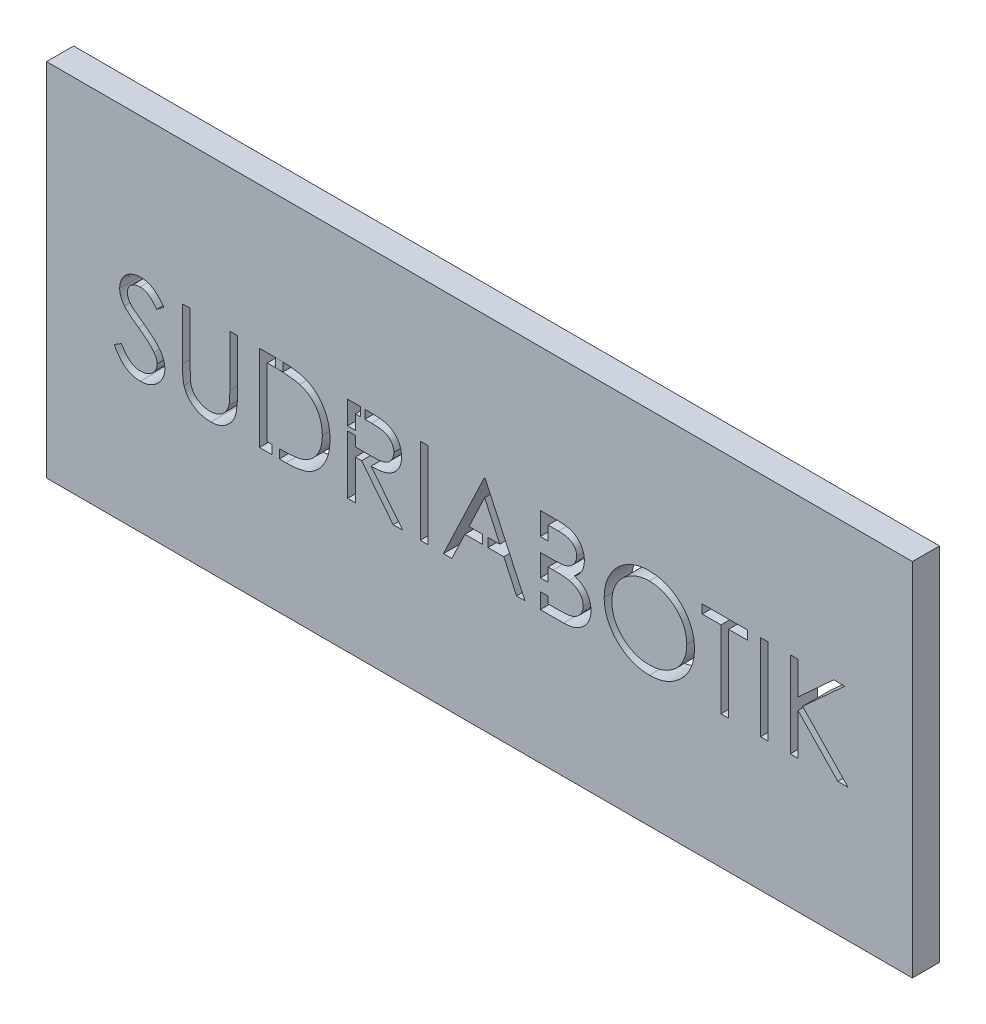
SolidWorks part; units mm, degrees
ref_plane "Plan de face" through (0, 0, 0) normal (0, 0, 1) x (1, 0, 0)
ref_plane "Plan de dessus" through (0, 0, 0) normal (0, 1, 0) x (1, 0, 0)
ref_plane "Plan de droite" through (0, 0, 0) normal (1, 0, 0) x (0, 0, -1)
sketch "Esquisse1" plane through (0, 0, 0) normal (0, 0, 1) x (1, 0, 0)
  line L0 (97.3951, 0) -> (-118.5049, 0) construction
  line L1 (-165, 119) -> (165, 119)
  line L2 (-165, 119) -> (-165, -119)
  line L3 (-165, -119) -> (165, -119)
  line L4 (165, 119) -> (165, -119)
  line L5 (0, 79.3588) -> (0, -79.3588) construction
  line L6 (-92.5, -55) -> (-77.5, -55)
  line L7 (-92.5, -55) -> (-92.5, -61)
  line L8 (-92.5, -61) -> (-77.5, -61)
  line L9 (-77.5, -55) -> (-77.5, -61)
  line L10 (-7.5, -55) -> (7.5, -55)
  line L11 (-7.5, -55) -> (-7.5, -61)
  line L12 (-7.5, -61) -> (7.5, -61)
  line L13 (7.5, -55) -> (7.5, -61)
  line L14 (77.5, -55) -> (92.5, -55)
  line L15 (77.5, -55) -> (77.5, -61)
  line L16 (77.5, -61) -> (92.5, -61)
  line L17 (92.5, -55) -> (92.5, -61)
  line L18 (-225.3679, 76) -> (203.1013, 76) construction
  line L19 (55, 99) -> (75, 99)
  line L20 (55, 99) -> (55, 93)
  line L21 (55, 93) -> (75, 93)
  line L22 (75, 99) -> (75, 93)
  line L23 (85, 99) -> (105, 99)
  line L24 (85, 99) -> (85, 93)
  line L25 (85, 93) -> (105, 93)
  line L26 (105, 99) -> (105, 93)
  circle A0 centre (-125, 76) radius 8
  circle A1 centre (125, 76) radius 8
  dimension "D23" = 16
  dimension "D24" = 16
  dimension "D1" = 238
  dimension "D2" = 330
  dimension "D3" = 165
  dimension "D4" = 119
  dimension "D5" = 15
  dimension "D6" = 6
  dimension "D7" = 6
  dimension "D8" = 15
  dimension "D9" = 6
  dimension "D10" = 15
  dimension "D11" = 70
  dimension "D12" = 70
  dimension "D13" = 58
  dimension "D14" = 72.5
  dimension "D15" = 6
  dimension "D16" = 20
  dimension "D17" = 20
  dimension "D18" = 6
  dimension "D19" = 10
  dimension "D20" = 60
  dimension "D21" = 20
  dimension "D22" = 20
  dimension "D25" = 40
  dimension "D26" = 40
  dimension "D27" = 195
extrude "Boss.-Extru.1" add sketch "Esquisse1" along normal blind 6
sketch "Esquisse2" plane through (0, 0, 6) normal (0, 0, 1) x (1, 0, 0)
  line L0 (243.146, 0) -> (-260.0003, 0) construction
  line L1 (0, 180.4713) -> (0, -129.6072) construction
  line L2 (165, 119) -> (-165, 119) construction
  line L3 (-115, 119) -> (-95, 119)
  line L4 (-115, 119) -> (-115, 125)
  line L5 (-115, 125) -> (-95, 125)
  line L6 (-95, 119) -> (-95, 125)
  line L7 (-165, 119) -> (-165, -119) construction
  line L8 (-45, 119) -> (-25, 119)
  line L9 (-45, 119) -> (-45, 125)
  line L10 (-45, 125) -> (-25, 125)
  line L11 (-25, 119) -> (-25, 125)
  line L12 (25, 119) -> (25, 125)
  line L13 (45, 125) -> (25, 125)
  line L14 (45, 119) -> (45, 125)
  line L15 (45, 119) -> (25, 119)
  line L16 (95, 119) -> (95, 125)
  line L17 (115, 125) -> (95, 125)
  line L18 (115, 119) -> (115, 125)
  line L19 (115, 119) -> (95, 119)
  line L20 (-115, 119) -> (-95, 119)
  line L21 (-115, 119) -> (-115, 125)
  line L22 (-115, 125) -> (-95, 125)
  line L23 (-95, 119) -> (-95, 125)
  line L24 (-45, 119) -> (-25, 119)
  line L25 (-45, 119) -> (-45, 125)
  line L26 (-45, 125) -> (-25, 125)
  line L27 (-25, 119) -> (-25, 125)
  line L28 (25, 119) -> (25, 125)
  line L29 (45, 125) -> (25, 125)
  line L30 (45, 119) -> (45, 125)
  line L31 (45, 119) -> (25, 119)
  line L32 (95, 119) -> (95, 125)
  line L33 (115, 125) -> (95, 125)
  line L34 (115, 119) -> (115, 125)
  line L35 (115, 119) -> (95, 119)
  line L36 (115, -119) -> (95, -119)
  line L37 (115, -119) -> (115, -125)
  line L38 (115, -125) -> (95, -125)
  line L39 (95, -119) -> (95, -125)
  line L40 (45, -119) -> (25, -119)
  line L41 (45, -119) -> (45, -125)
  line L42 (45, -125) -> (25, -125)
  line L43 (25, -119) -> (25, -125)
  line L44 (-25, -119) -> (-25, -125)
  line L45 (-45, -125) -> (-25, -125)
  line L46 (-45, -119) -> (-45, -125)
  line L47 (-45, -119) -> (-25, -119)
  line L48 (-95, -119) -> (-95, -125)
  line L49 (-115, -125) -> (-95, -125)
  line L50 (-115, -119) -> (-115, -125)
  line L51 (-115, -119) -> (-95, -119)
  line L52 (115, -119) -> (95, -119)
  line L53 (115, -119) -> (115, -125)
  line L54 (115, -125) -> (95, -125)
  line L55 (95, -119) -> (95, -125)
  line L56 (45, -119) -> (25, -119)
  line L57 (45, -119) -> (45, -125)
  line L58 (45, -125) -> (25, -125)
  line L59 (25, -119) -> (25, -125)
  line L60 (-25, -119) -> (-25, -125)
  line L61 (-45, -125) -> (-25, -125)
  line L62 (-45, -119) -> (-45, -125)
  line L63 (-45, -119) -> (-25, -119)
  line L64 (-95, -119) -> (-95, -125)
  line L65 (-115, -125) -> (-95, -125)
  line L66 (-115, -119) -> (-115, -125)
  line L67 (-115, -119) -> (-95, -119)
  line M9 (-165, -119) -> (165, -119)
  line M11 (165, 119) -> (-165, 119)
  dimension "D1" = 6
  dimension "D2" = 6
  dimension "D3" = 20
  dimension "D4" = 20
  dimension "D5" = 50
  dimension "D6" = 50
extrude "Boss.-Extru.2" add sketch "Esquisse2" against normal blind 6 contours L6 L5 L4 M11 | L11 L10 L9 M11 | L14 L13 L12 M11 | L18 L17 L16 M11 | L39 L38 L37 M9 | L43 L42 L41 M9 | L46 L45 L44 M9 | L50 L49 L48 M9 region at (-105, 122, 6) region at (105, 122, 6) region at (35, 122, 6) region at (-35, 122, 6) region at (105, -122, 6) region at (-105, -122, 6) region at (-35, -122, 6) region at (35, -122, 6)
sketch "Esquisse3" plane through (0, 0, 6) normal (0, 0, 1) x (1, 0, 0)
  line L0 (-165, 119) -> (-165, -119) construction
  line L1 (-165, 69) -> (-159, 69)
  line L2 (-165, 69) -> (-165, 89)
  line L3 (-165, 89) -> (-159, 89)
  line L4 (-159, 69) -> (-159, 89)
  line L5 (234.1368, 0) -> (-337.9213, 0) construction
  line L6 (-165, 29) -> (-159, 29)
  line L7 (-165, 29) -> (-165, 9)
  line L8 (-165, 9) -> (-159, 9)
  line L9 (-159, 29) -> (-159, 9)
  line L10 (0, 279.7488) -> (0, -188.1201) construction
  line L11 (-115, 119) -> (-165, 119) construction
  line L12 (-159, -29) -> (-159, -9)
  line L13 (-165, -9) -> (-159, -9)
  line L14 (-165, -29) -> (-165, -9)
  line L15 (-165, -29) -> (-159, -29)
  line L16 (-159, -69) -> (-159, -89)
  line L17 (-165, -89) -> (-159, -89)
  line L18 (-165, -69) -> (-165, -89)
  line L19 (-165, -69) -> (-159, -69)
  line L20 (165, -69) -> (159, -69)
  line L21 (165, -69) -> (165, -89)
  line L22 (165, -89) -> (159, -89)
  line L23 (159, -69) -> (159, -89)
  line L24 (165, -29) -> (159, -29)
  line L25 (165, -29) -> (165, -9)
  line L26 (165, -9) -> (159, -9)
  line L27 (159, -29) -> (159, -9)
  line L28 (159, 29) -> (159, 9)
  line L29 (165, 9) -> (159, 9)
  line L30 (165, 29) -> (165, 9)
  line L31 (165, 29) -> (159, 29)
  line L32 (159, 69) -> (159, 89)
  line L33 (165, 89) -> (159, 89)
  line L34 (165, 69) -> (165, 89)
  line L35 (165, 69) -> (159, 69)
  line L36 (153, -119) -> (153, -109)
  line L37 (-165, -119) -> (-153, -119)
  line L38 (-165, -119) -> (-165, -109)
  line L39 (-165, -109) -> (-153, -109)
  line L40 (-153, -119) -> (-153, -109)
  line L41 (165, -109) -> (153, -109)
  line L42 (165, -119) -> (165, -109)
  line L43 (165, -119) -> (153, -119)
  dimension "D1" = 40
  dimension "D2" = 6
  dimension "D3" = 6
  dimension "D4" = 20
  dimension "D5" = 20
  dimension "D6" = 30
  dimension "D7" = 12
  dimension "D8" = 10
extrude "Enlèv. mat.-Extru.1" cut sketch "Esquisse3" against normal blind 6
sketch "Esquisse4" plane through (0, 0, 6) normal (0, 0, 1) x (1, 0, 0)
  line L0 (-162, 122) -> (-162, -131.0602) construction
  line L1 (0, 158.5579) -> (0, -182.4489) construction
  line L2 (-115, 119) -> (-165, 119) construction
  line L3 (-106.4439, -58) -> (117.3944, -58) construction
  line L4 (-159, 89) -> (-165, 89) construction
  line L5 (-165, 119) -> (-165, 89) construction
  line L6 (-165, 69) -> (-159, 69) construction
  line L7 (-159, 29) -> (-165, 29) construction
  line L8 (-165, 9) -> (-159, 9) construction
  line L9 (-159, -9) -> (-165, -9) construction
  line L10 (-92.5, -55) -> (-92.5, -61) construction
  line L11 (-77.5, -61) -> (-77.5, -55) construction
  line L12 (-165, -29) -> (-159, -29) construction
  line L13 (-159, -69) -> (-165, -69) construction
  line L14 (-165, -89) -> (-159, -89) construction
  line L15 (-7.5, -55) -> (-7.5, -61) construction
  line L16 (162, 122) -> (162, -131.0602) construction
  line L17 (116.5184, 96) -> (43.4816, 96) construction
  line L18 (-126.5544, 122) -> (2.7821, 122) construction
  line L19 (-45, 119) -> (-95, 119) construction
  line L20 (-45, 119) -> (-45, 125) construction
  line L21 (75, 93) -> (75, 99) construction
  line L23 (55, 93) -> (75, 93) construction
  circle A0 centre (-162, 114) radius 1.5
  circle A1 centre (-162, 94) radius 1.5
  circle A2 centre (-162, 64) radius 1.5
  circle A3 centre (-162, 34) radius 1.5
  circle A4 centre (-162, 4) radius 1.5
  circle A5 centre (-105, 122) radius 1.5
  circle A6 centre (-162, -4) radius 1.5
  circle A7 centre (-162, -34) radius 1.5
  circle A8 centre (-162, -64) radius 1.5
  circle A9 centre (-162, -94) radius 1.5
  circle A10 centre (-97.5, -58) radius 1.5
  circle A11 centre (-72.5, -58) radius 1.5
  circle A12 centre (162, -94) radius 1.5
  circle A13 centre (162, -64) radius 1.5
  circle A14 centre (162, -34) radius 1.5
  circle A15 centre (162, -4) radius 1.5
  circle A16 centre (80, 96) radius 1.5
  circle A17 centre (162, 4) radius 1.5
  circle A18 centre (162, 34) radius 1.5
  circle A19 centre (162, 64) radius 1.5
  circle A20 centre (162, 94) radius 1.5
  circle A21 centre (162, 114) radius 1.5
  circle A22 centre (-12.5, -58) radius 1.5
  circle A23 centre (12.5, -58) radius 1.5
  circle A24 centre (72.5, -58) radius 1.5
  circle A25 centre (97.5, -58) radius 1.5
  circle A26 centre (-35, 122) radius 1.5
  circle A27 centre (35, 122) radius 1.5
  circle A28 centre (105, 122) radius 1.5
  dimension "D1" = 3
  dimension "D2" = 3
  dimension "D3" = 3
  dimension "D4" = 3
  dimension "D5" = 3
  dimension "D6" = 3
  dimension "D7" = 3
  dimension "D8" = 3
  dimension "D9" = 3
  dimension "D10" = 3
  dimension "D11" = 3
  dimension "D12" = 5
  dimension "D13" = 5
  dimension "D15" = 5
  dimension "D16" = 5
  dimension "D17" = 5
  dimension "D19" = 3
  dimension "D20" = 5
  dimension "D21" = 5
  dimension "D23" = 3
  dimension "D24" = 3
  dimension "D25" = 5
  dimension "D26" = 5
  dimension "D27" = 5
  dimension "D28" = 10
  dimension "D29" = 3
  dimension "D30" = 5
  dimension "D31" = 3
  dimension "D33" = 10
  dimension "D14" = 3
  dimension "D18" = 5
  dimension "D22" = 5
  dimension "D32" = 3
extrude "Enlèv. mat.-Extru.2" cut sketch "Esquisse4" against normal blind 6
sketch "Esquisse5" plane through (0, 0, 6) normal (0, 0, 1) x (1, 0, 0)
  line L1 (-200.0968, 0) -> (223.5072, 0)
  line L2 (-200.0968, 0) -> (-200.0968, -150.3561)
  line L3 (-200.0968, -150.3561) -> (223.5072, -150.3561)
  line L4 (223.5072, 0) -> (223.5072, -150.3561)
extrude "Enlèv. mat.-Extru.3" cut sketch "Esquisse5" against normal blind 6
sketch "Esquisse6" plane through (0, 0, 6) normal (0, 0, 1) x (1, 0, 0)
  line L0 (-165, 69) -> (-165, 29) construction
  line L2 (165, 0) -> (-165, 0) construction
  text T0 "SUDRIABOTIK" font "Century Gothic" height in points 72
  dimension "D1" = 83.5
  dimension "D2" = 29.5
extrude "Enlèv. mat.-Extru.4" cut sketch "Esquisse6" against normal blind 6
sketch "Esquisse7" plane through (0, 0, 6) normal (0, 0, 1) x (1, 0, 0)
  line L0 (-42.8696, 29.5) -> (-48.7731, 29.5) construction
  line L1 (-44.3875, 29.5) -> (-45.9701, 29.5)
  line L2 (-44.3875, 29.5) -> (-44.3875, 31.4538)
  line L3 (-44.3875, 31.4538) -> (-45.9701, 31.4538)
  line L4 (-45.9701, 29.5) -> (-45.9701, 31.4538)
  line L5 (-47.0635, 31.4538) -> (-44.8768, 31.4538) construction
  line L6 (-23.9531, 46.5962) -> (-27.525, 46.5962) construction
  line L7 (-45.1788, 46.5937) -> (-43.5909, 46.5937)
  line L8 (-45.1788, 46.5937) -> (-45.1788, 48.5305)
  line L9 (-45.1788, 48.5305) -> (-43.5909, 48.5305)
  line L10 (-43.5909, 46.5937) -> (-43.5909, 48.5305)
  line L11 (-26.3286, 46.5962) -> (-25.4223, 46.5962)
  line L12 (-26.3286, 46.5962) -> (-26.3286, 48.55)
  line L13 (-26.3286, 48.55) -> (-25.4223, 48.55)
  line L14 (-25.4223, 46.5962) -> (-25.4223, 48.55)
  line L15 (-27.525, 46.5962) -> (-27.525, 40.2462) construction
  line L16 (-27.525, 43.4212) -> (-29.2346, 43.4212)
  line L17 (-27.525, 43.4212) -> (-27.525, 42.4505)
  line L18 (-27.525, 42.4505) -> (-29.2346, 42.4505)
  line L19 (-29.2346, 43.4212) -> (-29.2346, 42.4505)
  line L20 (-29.2346, 29.5) -> (-29.2346, 48.55) construction
  line L21 (-2.2967, 37.5596) -> (4.5112, 37.5596) construction
  line L22 (0.6712, 37.5596) -> (1.8879, 37.5596)
  line L23 (0.6712, 37.5596) -> (0.6712, 35.6058)
  line L24 (0.6712, 35.6058) -> (1.8879, 35.6058)
  line L25 (1.8879, 37.5596) -> (1.8879, 35.6058)
  line L26 (5.4118, 35.6058) -> (-3.224, 35.6058) construction
  line L27 (15.2154, 46.5962) -> (15.2154, 40.4904) construction
  line L28 (15.2154, 43.5433) -> (13.5058, 43.5433)
  line L29 (15.2154, 43.5433) -> (15.2154, 40.4904)
  line L30 (15.2154, 40.4904) -> (13.5058, 40.4904)
  line L31 (13.5058, 43.5433) -> (13.5058, 40.4904)
  line L32 (13.5058, 29.5) -> (13.5058, 48.55) construction
  line L33 (15.2154, 38.5365) -> (15.2154, 31.4538) construction
  line L34 (15.2154, 32.964) -> (13.5058, 32.964)
  line L35 (15.2154, 32.964) -> (15.2154, 35.6058)
  line L36 (15.2154, 35.6058) -> (13.5058, 35.6058)
  line L37 (13.5058, 32.964) -> (13.5058, 35.6058)
  spline S0 degree 3 poles (-39.8701, 46.0619) (-40.0299, 46.1061) (-40.3695, 46.2) (-40.9238, 46.3025) (-41.5477, 46.3928) (-42.2438, 46.4694) (-43.0115, 46.5243) (-43.8512, 46.5655) (-44.7634, 46.5933) (-45.3958, 46.5952) (-45.724, 46.5962) knots 0 0 0 0 0.084319 0.179285 0.286583 0.405111 0.535593 0.67819 0.832976 1 1 1 1 construction
  spline S1 degree 3 poles (-44.9264, 48.55) (-44.5919, 48.5476) (-43.9455, 48.5429) (-43.0114, 48.5134) (-42.1472, 48.4612) (-41.3556, 48.3852) (-40.6345, 48.2918) (-39.986, 48.1748) (-39.4066, 48.0366) (-39.0502, 47.9188) (-38.8817, 47.8631) knots 0 0 0 0 0.164289 0.317406 0.458844 0.589367 0.707831 0.81577 0.91288 1 1 1 1 construction
extrude "Boss.-Extru.5" add sketch "Esquisse7" against normal blind 6
sketch "Esquisse8" plane through (0, 0, 6) normal (0, 0, 1) x (1, 0, 0)
  line L0 (-96.0144, 80) -> (-96.0144, 0)
  line L1 (165, 0) -> (-165, 0) construction
  line L2 (-96.0144, 0) -> (-187.5965, 0)
  line L3 (-187.5965, 0) -> (-187.5965, 141.8457)
  line L4 (-187.5965, 141.8457) -> (176.0356, 141.8457)
  line L5 (176.0356, 141.8457) -> (176.0356, 0)
  line L6 (176.0356, 0) -> (96.0356, 0)
  line L7 (96.0356, 0) -> (96.0356, 80)
  line L8 (96.0356, 80) -> (-96.0144, 80)
  dimension "D1" = 192.05
  dimension "D2" = 80
  dimension "D3" = 80
  dimension "D4" = 15
  dimension "D5" = 15.0029
extrude "Enlèv. mat.-Extru.5" cut sketch "Esquisse8" against normal blind 6
equation "\"D3@Esquisse1\"=\"D2@Esquisse1\"/2"
equation "\"D4@Esquisse1\"=\"D1@Esquisse1\"/2"
